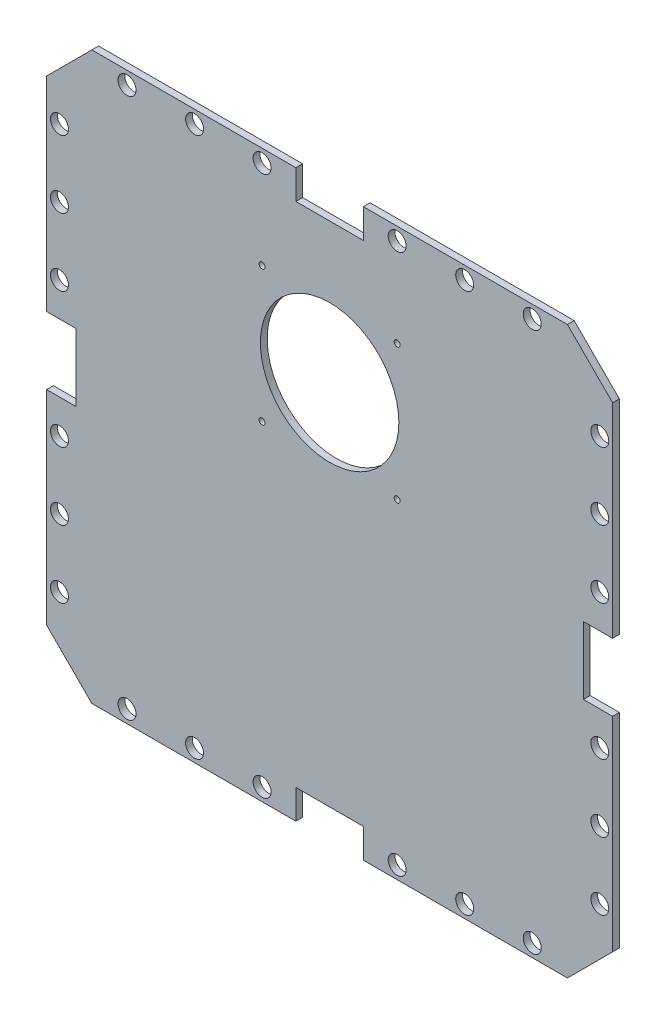
SolidWorks part; units mm, degrees
ref_plane "Front Plane" through (0, 0, 0) normal (0, 0, 1) x (1, 0, 0)
ref_plane "Top Plane" through (0, 0, 0) normal (0, 1, 0) x (1, 0, 0)
ref_plane "Right Plane" through (0, 0, 0) normal (1, 0, 0) x (0, 0, -1)
sketch "Sketch1" plane through (0, 0, 0) normal (0, 0, 1) x (1, 0, 0)
  line L0 (30.226, -4.826) -> (55.626, -4.826) construction
  line L1 (0, 0) -> (212.852, 0)
  line L2 (0, 0) -> (0, -212.852)
  line L3 (0, -212.852) -> (212.852, -212.852)
  line L4 (212.852, 0) -> (212.852, -212.852)
  line L5 (55.626, -4.826) -> (81.026, -4.826) construction
  line L6 (81.026, -4.826) -> (106.426, -4.826) construction
  line L7 (106.426, -4.826) -> (131.826, -4.826) construction
  line L8 (131.826, -4.826) -> (157.226, -4.826) construction
  line L9 (157.226, -4.826) -> (182.626, -4.826) construction
  line L10 (106.426, 0) -> (106.426, -212.852) construction
  line L11 (0, -106.426) -> (212.852, -106.426) construction
  line L12 (16.9978, 0) -> (0, -16.9978)
  line L13 (212.852, -16.9978) -> (195.8542, 0)
  line L14 (195.8542, -212.852) -> (212.852, -195.8542)
  line L15 (0, -195.8542) -> (16.9978, -212.852)
  line L16 (93.726, 0) -> (93.726, -11)
  line L17 (81.026, -38.2041) -> (131.826, -38.2042) construction
  line L18 (81.026, -38.2041) -> (81.026, -89.0042) construction
  line L19 (81.026, -89.0042) -> (131.826, -89.0042) construction
  line L20 (131.826, -38.2042) -> (131.826, -89.0042) construction
  line L21 (106.426, -89.0042) -> (106.426, -38.2041) construction
  line L22 (81.026, -63.6041) -> (131.826, -63.6041) construction
  line L23 (93.726, -11) -> (119.126, -11)
  line L24 (119.126, -11) -> (119.126, 0)
  line L25 (212.852, -93.726) -> (201.852, -93.726)
  line L26 (201.852, -93.726) -> (201.852, -119.126)
  line L27 (201.852, -119.126) -> (212.852, -119.126)
  line L28 (119.126, -212.852) -> (119.126, -201.852)
  line L29 (119.126, -201.852) -> (93.726, -201.852)
  line L30 (93.726, -201.852) -> (93.726, -212.852)
  line L31 (0, -119.126) -> (11, -119.126)
  line L32 (11, -119.126) -> (11, -93.726)
  line L33 (11, -93.726) -> (0, -93.726)
  circle A0 centre (30.226, -4.826) radius 3.38
  circle A1 centre (55.626, -4.826) radius 3.38
  circle A2 centre (81.026, -4.826) radius 3.38
  circle A3 centre (131.826, -4.826) radius 3.38
  circle A4 centre (157.226, -4.826) radius 3.38
  circle A5 centre (182.626, -4.826) radius 3.38
  circle A6 centre (106.426, -4.826) radius 5.1943
  circle A7 centre (208.026, -182.626) radius 3.38
  circle A8 centre (208.026, -157.226) radius 3.38
  circle A9 centre (208.026, -131.826) radius 3.38
  circle A10 centre (208.026, -106.426) radius 5.1943
  circle A11 centre (208.026, -81.026) radius 3.38
  circle A12 centre (208.026, -55.626) radius 3.38
  circle A13 centre (208.026, -30.226) radius 3.38
  circle A14 centre (30.226, -208.026) radius 3.38
  circle A15 centre (55.626, -208.026) radius 3.38
  circle A16 centre (81.026, -208.026) radius 3.38
  circle A17 centre (106.426, -208.026) radius 5.1943
  circle A18 centre (131.826, -208.026) radius 3.38
  circle A19 centre (157.226, -208.026) radius 3.38
  circle A20 centre (182.626, -208.026) radius 3.38
  circle A21 centre (4.826, -30.226) radius 3.38
  circle A22 centre (4.826, -55.626) radius 3.38
  circle A23 centre (4.826, -81.026) radius 3.38
  circle A24 centre (4.826, -106.426) radius 5.1943
  circle A25 centre (4.826, -131.826) radius 3.38
  circle A26 centre (4.826, -157.226) radius 3.38
  circle A27 centre (4.826, -182.626) radius 3.38
  circle A28 centre (106.426, -63.6041) radius 26.035
  circle A29 centre (81.026, -38.2041) radius 1.13
  circle A30 centre (131.826, -38.2042) radius 1.13
  circle A31 centre (131.826, -89.0042) radius 1.13
  circle A32 centre (81.026, -89.0042) radius 1.13
  point P14 (106.426, -106.426)
  point P69 (106.426, -106.426)
  point P78 (106.426, -106.426)
  point P88 (106.426, -11)
  point P91 (192.9842, -117.2762)
  point P92 (0, 0)
  point P104 (106.426, -106.426)
  point P105 (197.852, -139.2034)
  point P106 (0, 0)
  dimension "D1" = 6.76
  dimension "D5" = 10.3886
  dimension "D13" = 52.07
  dimension "D14" = 2.26
  dimension "D2" = 30.226
  dimension "D3" = 25.4
  dimension "D4" = 4.826
  dimension "D6" = 212.852
  dimension "D7" = 212.852
  dimension "D9" = 45
  dimension "D10" = 24.0386
  dimension "D12" = 63.6041
  dimension "D15" = 50.8
  dimension "D16" = 25.4
  dimension "D17" = 11
  dimension "D8" = 4
  dimension "D11" = 4
  dimension "D18" = 4
extrude "Boss-Extrude1" add sketch "Sketch1" along normal blind 2.54 contours A24 L2 L3 A17 L4 A10 L1 A6 A27 A26 A25 A23 A22 A21 A20 A19 A18 A16 A15 A14 A13 A12 A11 A9 A8 A7 A5 region at (106.426, -108.6887, 0)
hole_wizard "#4-40 Tapped Hole1" positions "3DSketch1" profile "Sketch2" tap size "#4-40" standard "ANSI Inch" end condition through all
sketch3d "3DSketch1"
  line L0 (81.026, -38.2041, 2.54) -> (81.026, -38.2041, 0) construction
  line L1 (131.826, -38.2042, 2.54) -> (131.826, -38.2042, 0) construction
  line L2 (131.826, -89.0042, 2.54) -> (131.826, -89.0042, 0) construction
  line L3 (81.026, -89.0042, 2.54) -> (81.026, -89.0042, 0) construction
  point P0 (81.026, -38.2041, 2.54)
  point P4 (131.826, -38.2042, 2.54)
  point P8 (131.826, -89.0042, 2.54)
  point P12 (81.026, -89.0042, 2.54)
sketch "Sketch2" plane through (81.026, -38.2041, 2.54) normal (1, 0, 0) x (0, -1, 0)
  line L0 (0, 0) -> (0, 2.54)
  line L1 (0, 2.54) -> (1.1303, 2.54)
  line L2 (1.1303, 2.54) -> (1.1303, 0)
  line L5 (1.1303, 0) -> (0, 0)
  line L11 (0, -6.35) -> (0, 107.95) construction
  dimension "Thru Tap Drill Dia." = 2.2606
  dimension "Thru Tap Drill Depth" = 2.54
cosmetic thread "Hole Thread1" parameters "D2"=2.8448
cosmetic thread "Hole Thread2" parameters "D2"=2.8448
cosmetic thread "Hole Thread3" parameters "D2"=2.8448
cosmetic thread "Hole Thread4" parameters "D2"=2.8448
